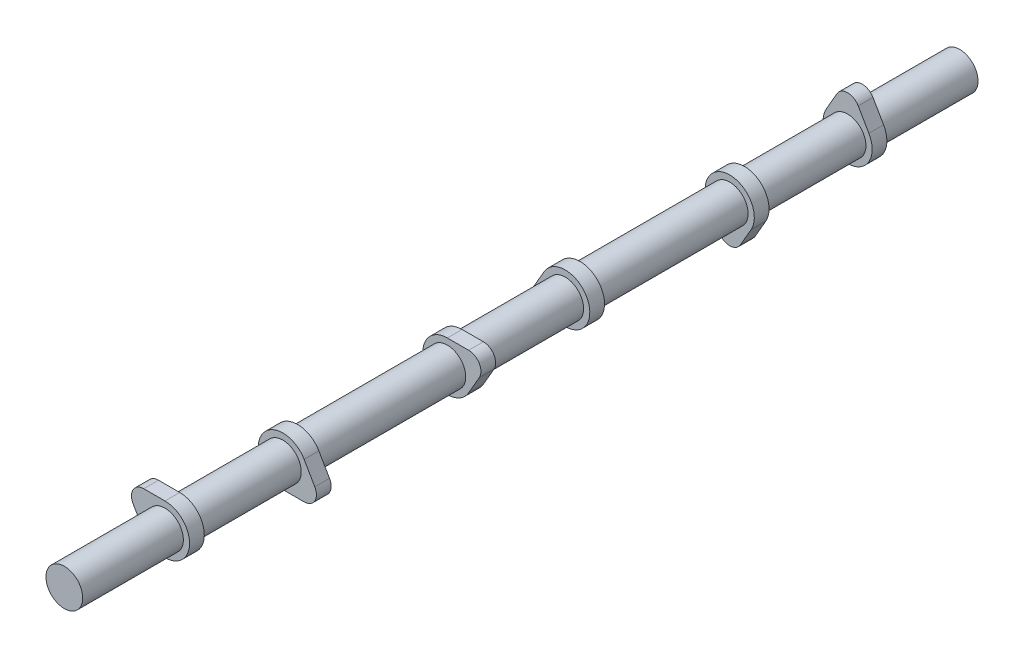
SolidWorks part; units mm, degrees
material "Plain Carbon Steel"
ref_plane "Front Plane" through (0, 0, 0) normal (0, 0, 1) x (1, 0, 0)
ref_plane "Top Plane" through (0, 0, 0) normal (0, 1, 0) x (1, 0, 0)
ref_plane "Right Plane" through (0, 0, 0) normal (1, 0, 0) x (0, 0, -1)
sketch "Sketch1" plane through (0, 0, 0) normal (0, 0, 1) x (1, 0, 0)
  line L0 (-5.4993, 15.875) -> (-10.9985, 6.35)
  line L1 (5.4993, 15.875) -> (10.9985, 6.35)
  arc A0 (-10.9985, 6.35) -> (10.9985, 6.35) centre (0, 0) ccw
  arc A1 (5.4993, 15.875) -> (-5.4993, 15.875) centre (0, 12.7) ccw
  dimension "D1" = 25.4
  dimension "D2" = 12.7
  dimension "D3" = 12.7
extrude "Boss-Extrude1" add sketch "Sketch1" along normal blind 7.62
ref_axis "Axis1" through (0, 0, 276.4636) along (0, 0, -1)
move or copy body "Body-Move/Copy1" bodies to move or copy 101 copy yes number of copies 1 translate (0, 0, 60.96)
move or copy body "Body-Move/Copy2" bodies to move or copy 102 copy no rotation origin (0, 0, 0) rotation axis (0, 0, 1) rotation angle 180
sketch "Sketch2" plane through (0, 0, 0) normal (0, 0, 1) x (1, 0, 0)
  circle A0 centre (0, 0) radius 9.5
  dimension "D1" = 19
extrude "Boss-Extrude2" add sketch "Sketch2" along normal blind 146.05 from offset 25.4 offset against normal yes
pattern_linear "LPattern1" count 3 spacing 146.05 along (0, 0, -1) of bodies 104
move or copy body "Body-Move/Copy3" bodies to move or copy 105 copy no rotation origin (0, 0, 0) rotation axis (0, 0, 1) rotation angle 120
move or copy body "Body-Move/Copy4" bodies to move or copy 104 copy no rotation origin (0, 0, 0) rotation axis (0, 0, -1) rotation angle 120
sketch "Sketch3" plane through (0, 0, -317.5) normal (0, 0, -1) x (-1, 0, 0)
  circle A1 centre (0, 0) radius 9.5
  circle A2 centre (0, 0) radius 9.5
  dimension "D1" = 0
extrude "Boss-Extrude3" add sketch "Sketch3" along normal blind 24.94
combine bodies "Combine1" operation type add bodies to combine 108 107 109
